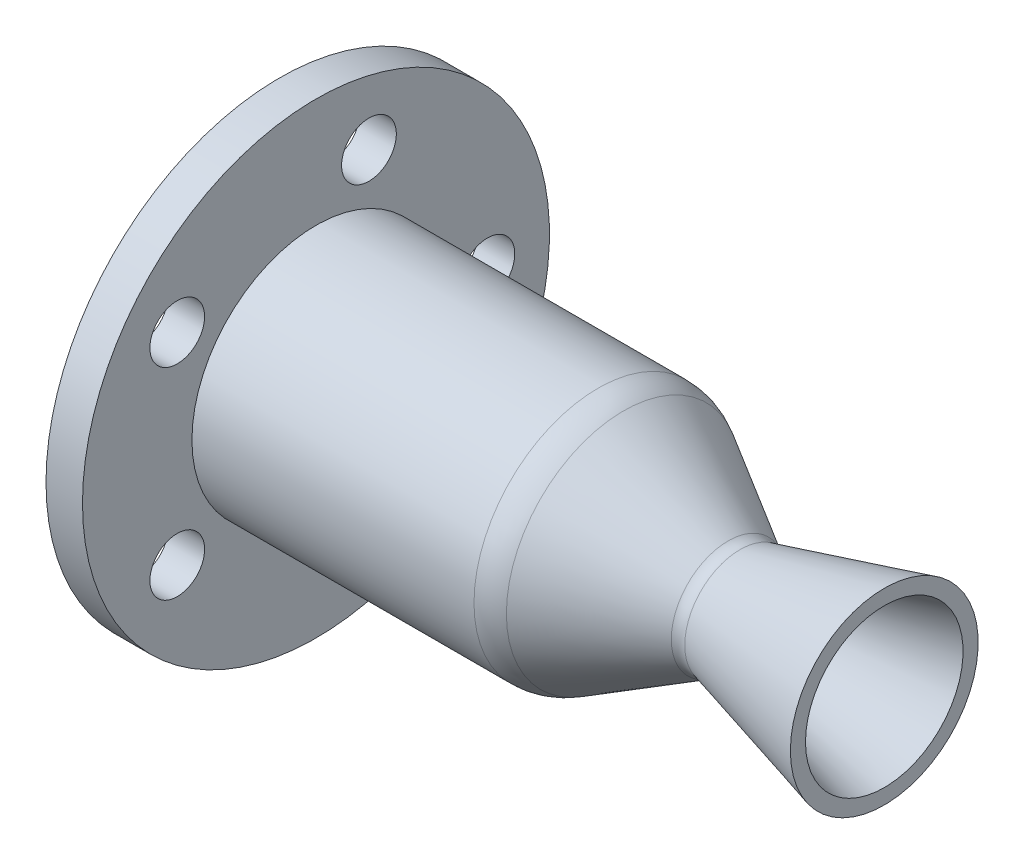
SolidWorks part; units mm, degrees
material "AISI 304"
ref_plane "Front Plane" through (0, 0, 0) normal (0, 0, 1) x (1, 0, 0)
ref_plane "Top Plane" through (0, 0, 0) normal (0, 1, 0) x (1, 0, 0)
ref_plane "Right Plane" through (0, 0, 0) normal (1, 0, 0) x (0, 0, -1)
sketch "Sketch1" plane through (0, 0, 0) normal (0, 0, 1) x (1, 0, 0)
  line L0 (0, 0) -> (366.3783, 0) construction
  line L1 (0, 0) -> (0, 38.1) construction
  line L2 (0, 38.1) -> (110.897, 38.1)
  line L3 (158.9188, 24.511) -> (158.9188, 13.97) construction
  line L4 (117.247, 36.3985) -> (153.6483, 15.3822)
  line L5 (150.9294, 13.97) -> (106.9103, 13.97) construction
  line L6 (161.647, 14.3292) -> (210.5452, 27.4314)
  line L7 (210.5452, 27.4314) -> (210.5452, 0) construction
  line L8 (12.7, 43.18) -> (110.897, 43.18)
  line L9 (119.787, 40.7979) -> (156.1883, 19.7816)
  line L10 (160.3322, 19.2361) -> (210.5452, 32.6906)
  line L11 (0, 43.18) -> (0, 38.1)
  line L12 (210.5452, 27.4314) -> (210.5452, 32.6906)
  line L13 (160.3322, 19.2361) -> (209.2304, 32.3383) construction
  line L14 (0, 43.18) -> (0, 81.28)
  line L15 (0, 81.28) -> (12.7, 81.28)
  line L16 (12.7, 81.28) -> (12.7, 43.18)
  line L17 (0, 43.18) -> (110.897, 43.18) construction
  arc A0 (153.6483, 15.3822) -> (161.647, 14.3292) centre (158.9188, 24.511) ccw
  arc A1 (110.897, 38.1) -> (117.247, 36.3985) centre (110.897, 25.4) cw
  arc A2 (110.897, 43.18) -> (119.787, 40.7979) centre (110.897, 25.4) cw
  arc A3 (156.1883, 19.7816) -> (160.3322, 19.2361) centre (158.9188, 24.511) ccw
  point P16 (114.3, 38.1)
  dimension "D4" = 21.082
  dimension "D9" = 12.7
  dimension "D1" = 38.1
  dimension "D2" = 114.3
  dimension "D3" = 13.97
  dimension "D5" = 30
  dimension "D6" = 15
  dimension "D7" = 27.4314
  dimension "D11" = 12.7
  dimension "D12" = 38.1
  dimension "D10" = 5.08
revolve "Revolve1" add sketch "Sketch1" angle 360 about L0
sketch "Sketch2" plane through (0, 0, 0) normal (-1, 0, 0) x (0, 0, 1)
  line L0 (-38.1, 0) -> (-81.28, 0) construction
  circle A0 centre (0, 0) radius 38.1 construction
  circle A1 centre (0, 0) radius 38.1 construction
  circle A2 centre (0, 0) radius 81.28 construction
  circle A3 centre (-59.69, 0) radius 9.525
  circle A4 centre (-18.4452, 56.7686) radius 9.525
  circle A5 centre (48.2902, 35.0849) radius 9.525
  circle A6 centre (48.2902, -35.0849) radius 9.525
  circle A7 centre (-18.4452, -56.7686) radius 9.525
  point P11 (-23.4605, 46.8031)
  point P12 (0, 0)
  point P22 (0, 0)
  dimension "D1" = 19.05
  dimension "D2" = 5
extrude "Cut-Extrude1" cut sketch "Sketch2" against normal through all
equation "\"l_star\"= .8m'characteristic length"
equation "\"R_t\"= .55in'throat radius"
equation "\"V_c\"= \"l_star\" * \"R_t\"'chamber volume"
equation "\"D_c\"= 3in'chamber diameter"
equation "\"L_c\"= \"V_c\" / ( ( pi * \"D_c\" ) / 4 )'chamber length"
equation "\"eps_x\"= 3.8557'expansion ratio"
equation "\"D_e\" = \"R_t\" * 2 * sqr ( \"eps_x\" )'exit diameter"
equation "\"arc_t\"= 1.5in * \"R_t\"'arc between convergent and divergent"
equation "\"D3@Sketch1\"=\"R_t\""
equation "\"D7@Sketch1\"=\"D_e\"/2"
equation "\"D1@Sketch1\"=\"D_c\"/2"
